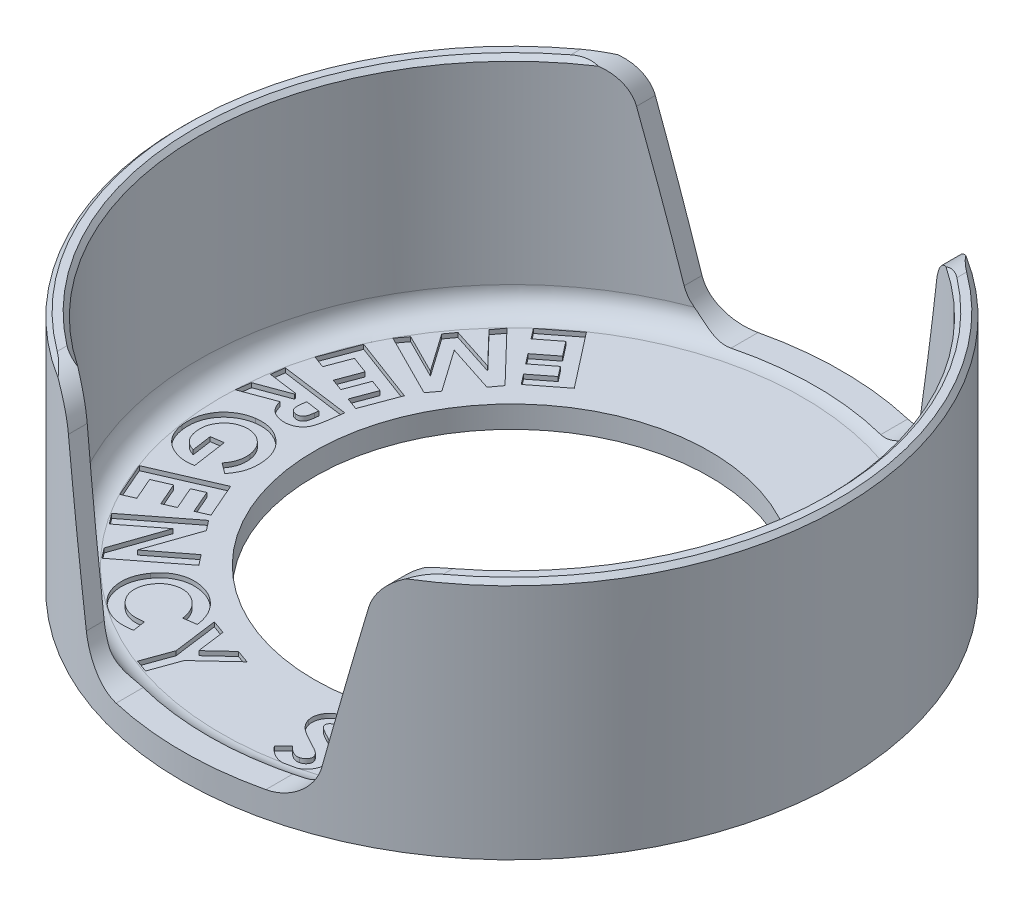
SolidWorks part; units mm, degrees
ref_plane "Front Plane" through (0, 0, 0) normal (0, 0, 1) x (1, 0, 0)
ref_plane "Top Plane" through (0, 0, 0) normal (0, 1, 0) x (1, 0, 0)
ref_plane "Right Plane" through (0, 0, 0) normal (1, 0, 0) x (0, 0, -1)
sketch "Sketch1" plane through (0, 0, 0) normal (0, 1, 0) x (1, 0, 0)
  circle A0 centre (0, 0) radius 37.5
  circle A1 centre (0, 0) radius 22.5
  dimension "D1" = 75
  dimension "D2" = 45
extrude "Boss-Extrude1" add sketch "Sketch1" along normal blind 2.5
sketch "Sketch2" plane through (0, 2.5, 0) normal (0, 1, 0) x (1, 0, 0)
  circle A0 centre (0, 0) radius 35.6108
  circle A1 centre (0, 0) radius 37.5
extrude "Boss-Extrude2" add sketch "Sketch2" along normal blind 25
fillet "Fillet1" radius 2.5 1 edges at (0, 2.5, 35.6108)
chamfer "Chamfer1" distance 0.5 angle 45 2 edges at (0, 27.5, 37.5) (0, 27.5, 35.6108)
sketch "Sketch3" plane through (0, 0, 0) normal (0, 0, 1) x (1, 0, 0)
  line L6 (-17.9393, 27.5) -> (17.9393, 27.5)
  line L8 (36.1108, 27.5) -> (-36.1108, 27.5) construction
  line L9 (-17.9393, 27.5) -> (-12.5381, 2.9295)
  line L10 (12.5381, 2.9295) -> (17.9393, 27.5)
  line L11 (-12.5381, 2.9295) -> (12.5381, 2.9295)
  point P6 (0, 0)
  point P12 (0, 27)
  point P15 (0, 27.5)
extrude "Cut-Extrude2" cut sketch "Sketch3" against normal mid plane 109
fillet "Fillet2" radius 5 8 edges at (17.9393, 27.5, 31.8499) (12.5381, 2.9295, 33.7478) (-12.5381, 2.9295, 33.7478) (-12.5381, 2.9295, -33.7478) (12.5381, 2.9295, -33.7478) (17.9393, 27.5, -31.8499) (-17.9393, 27.5, -31.8499) (-17.9393, 27.5, 31.8499)
sketch "Sketch4" plane through (0, 2.5, 0) normal (0, 1, 0) x (1, 0, 0)
  text T0 "<b>                            EMERGENCY</b>" font "Century Gothic" height in points 30
  text T1 "<b> STOP</b>" font "Century Gothic" height in points 30
extrude "Cut-Extrude3" cut sketch "Sketch4" against normal blind 0.5
